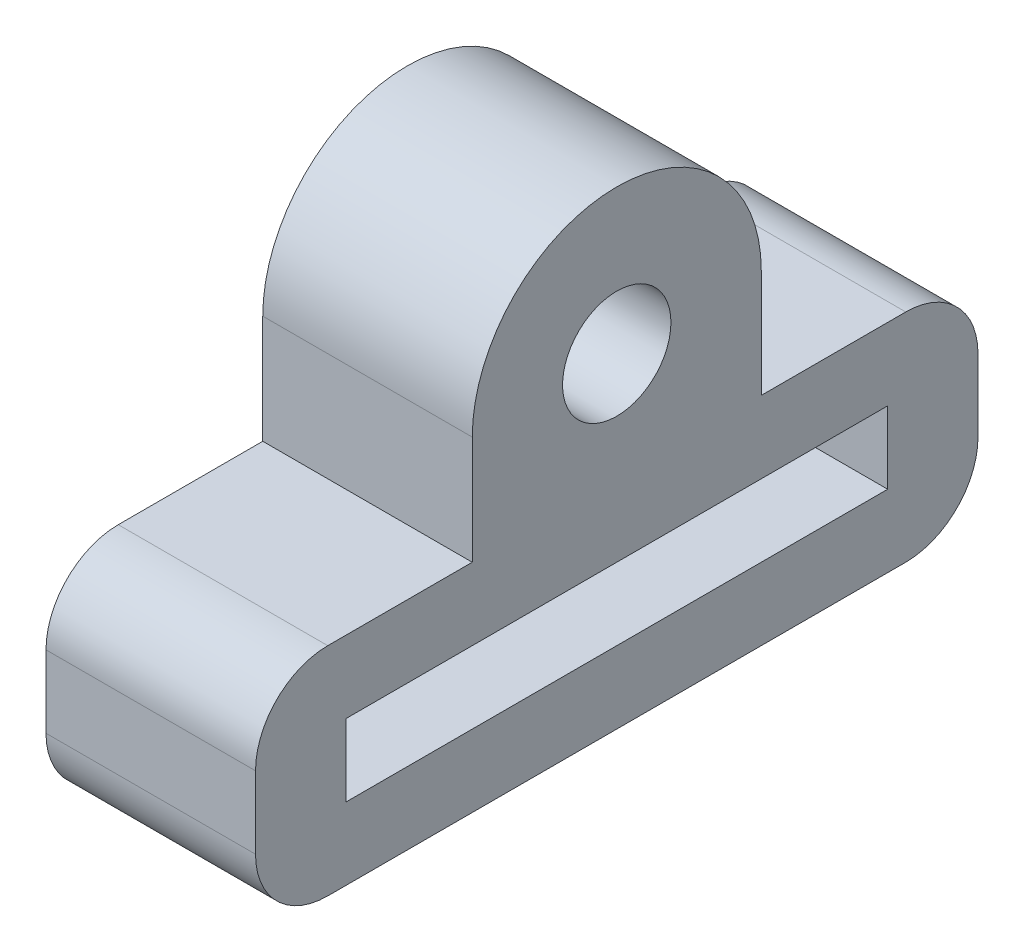
SolidWorks part; units mm, degrees
ref_plane "Alzado" through (0, 0, 0) normal (0, 0, 1) x (1, 0, 0)
ref_plane "Planta" through (0, 0, 0) normal (0, 1, 0) x (1, 0, 0)
ref_plane "Vista lateral" through (0, 0, 0) normal (1, 0, 0) x (0, 0, -1)
sketch "Croquis1" plane through (0, 0, 0) normal (1, 0, 0) x (0, 0, -1)
  line L2 (-10, 1) -> (-10, -1)
  line L3 (-8, -3) -> (8, -3)
  line L4 (10, 1) -> (10, -1)
  line L5 (-10, 3) -> (10, -3) construction
  line L6 (-10, -3) -> (10, 3) construction
  line L7 (-7.5, 1) -> (7.5, 1)
  line L8 (-7.5, 1) -> (-7.5, -1)
  line L9 (-7.5, -1) -> (7.5, -1)
  line L10 (7.5, 1) -> (7.5, -1)
  line L11 (-7.5, 1) -> (7.5, -1) construction
  line L12 (-7.5, -1) -> (7.5, 1) construction
  line L15 (-10, 3) -> (10, 3) construction
  line L27 (-4, 3) -> (-8, 3)
  line L28 (4, 3) -> (8, 3)
  line L35 (0, 3) -> (0, 6) construction
  line L36 (-4, 6) -> (-4, 3)
  line L39 (4, 6) -> (4, 3)
  circle A1 centre (0, 6) radius 1.5
  arc A2 (4, 6) -> (-4, 6) centre (0, 6) ccw
  arc A3 (8, -3) -> (10, -1) centre (8, -1) ccw
  arc A4 (8, 3) -> (10, 1) centre (8, 1) cw
  arc A5 (-10, -1) -> (-8, -3) centre (-8, -1) ccw
  arc A6 (-8, 3) -> (-10, 1) centre (-8, 1) ccw
  point P0 (0, 0)
  point P6 (0, 0)
  dimension "D18" = 8
  dimension "D17" = 3
  dimension "D6" = 2
  dimension "D2" = 20
  dimension "D3" = 2
  dimension "D4" = 15
  dimension "D5" = 6
  dimension "D16" = 3
  dimension "D23" = 2
extrude "Saliente-Extruir1" add sketch "Croquis1" along normal mid plane 5.8
